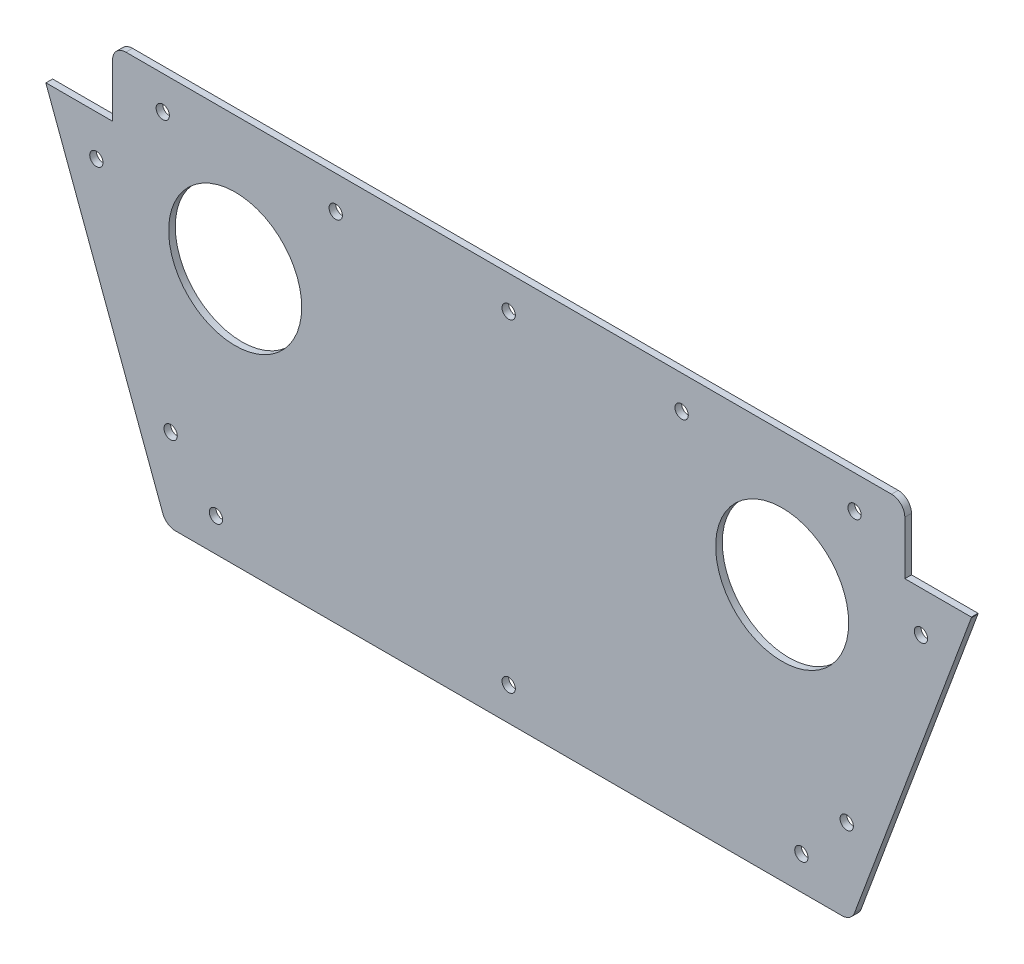
SolidWorks part; units mm, degrees
ref_plane "前基準面" through (0, 0, 0) normal (0, 0, 1) x (1, 0, 0)
ref_plane "上基準面" through (0, 0, 0) normal (0, 1, 0) x (1, 0, 0)
ref_plane "右基準面" through (0, 0, 0) normal (1, 0, 0) x (0, 0, -1)
sketch "草圖1" plane through (0, 0, 0) normal (0, 0, 1) x (1, 0, 0)
  line L0 (-69.55, 38.6) -> (69.55, 38.6)
  line L1 (69.55, 38.6) -> (69.55, 28.5)
  line L2 (69.55, 28.5) -> (51.5, -20)
  line L3 (51.5, -20) -> (-51.5, -20)
  line L4 (-51.5, -20) -> (-69.55, 28.5)
  line L5 (-69.55, 28.5) -> (-69.55, 38.6)
  dimension "D1" = 10.1
  dimension "D2" = 10.1
  dimension "D3" = 58.6
  dimension "D4" = 139.1
  dimension "D5" = 69.55
  dimension "D6" = 103
  dimension "D7" = 51.5
  dimension "D8" = 20
sheet metal parameters "鈑金1" thickness 1 parameters "D1"=0.7366, "厚度"=1
base flange "基材-凸緣1" sketch "草圖1" thickness 1 reverse thickness direction no parameters "D1"=0.7366
sketch "草圖3" plane through (0, 0, 0) normal (0, 0, 1) x (1, 0, 0)
  line L0 (-66.113, 33.6) -> (-48.0258, -15) construction
  line L1 (-48.0258, -15) -> (48.0258, -15) construction
  line L2 (48.0258, -15) -> (66.113, 33.6) construction
  line L3 (66.113, 33.6) -> (-66.113, 33.6) construction
  line L4 (69.55, 38.6) -> (-69.55, 38.6) construction
  line L5 (-69.55, 28.5) -> (-51.5, -20) construction
  line L6 (51.5, -20) -> (69.55, 28.5) construction
  line L7 (-51.5, -20) -> (51.5, -20) construction
  line L9 (-69.55, 38.6) -> (-59.55, 38.6)
  line L10 (-69.55, 38.6) -> (-69.55, 28.6)
  line L11 (-69.55, 28.6) -> (-59.55, 28.6)
  line L12 (-59.55, 38.6) -> (-59.55, 28.6)
  line L13 (69.55, 38.6) -> (59.55, 38.6)
  line L14 (69.55, 38.6) -> (69.55, 28.6)
  line L15 (69.55, 28.6) -> (59.55, 28.6)
  line L16 (59.55, 38.6) -> (59.55, 28.6)
  circle A0 centre (0, -15) radius 1
  circle A1 centre (44, -15) radius 1
  circle A2 centre (-44, -15) radius 1
  circle A3 centre (-50.8161, -7.5024) radius 1
  circle A4 centre (-61.9775, 22.488) radius 1
  circle A5 centre (0, 33.6) radius 1
  circle A6 centre (-26, 33.6) radius 1
  circle A7 centre (-52, 33.6) radius 1
  circle A8 centre (26, 33.6) radius 1
  circle A9 centre (52, 33.6) radius 1
  circle A10 centre (61.9775, 22.488) radius 1
  circle A11 centre (50.8161, -7.5024) radius 1
  circle A12 centre (-41.113, 18.6) radius 10
  circle A13 centre (41.113, 18.6) radius 10
  dimension "D19" = 2
  dimension "D24" = 20
  dimension "D25" = 20
  dimension "D1" = 5
  dimension "D2" = 5
  dimension "D3" = 5
  dimension "D4" = 5
  dimension "D5" = 10
  dimension "D6" = 10
  dimension "D7" = 10
  dimension "D8" = 10
  dimension "D9" = 7.55
  dimension "D10" = 7.55
  dimension "D11" = 26
  dimension "D12" = 26
  dimension "D13" = 44
  dimension "D14" = 44
  dimension "D15" = 32
  dimension "D16" = 32
  dimension "D17" = 8
  dimension "D18" = 8
  dimension "D20" = 25
  dimension "D21" = 25
  dimension "D22" = 20
  dimension "D23" = 20
extrude "除料-伸長1" cut sketch "草圖3" against normal blind 2 normal cut yes
fillet "圓角1" radius 2 4 edges at (-59.55, 38.6, -0.5) (-51.5, -20, -0.5) (51.5, -20, -0.5) (59.55, 38.6, -0.5)
flat pattern "平板-型式1" [suppressed]
sketch "彎折-線1" plane through (0, 0, 0) normal (0, 1, 0) x (1, 0, 0)
sketch3d "邊界方塊1" [suppressed]
  line L0 (69.55, -20, 0) -> (-69.55, -20, 0) construction
  line L1 (69.55, 38.6, 0) -> (-69.55, 38.6, 0) construction
  line L2 (69.55, -20, 0) -> (69.55, 38.6, 0) construction
  line L3 (-69.55, -20, 0) -> (-69.55, 38.6, 0) construction
